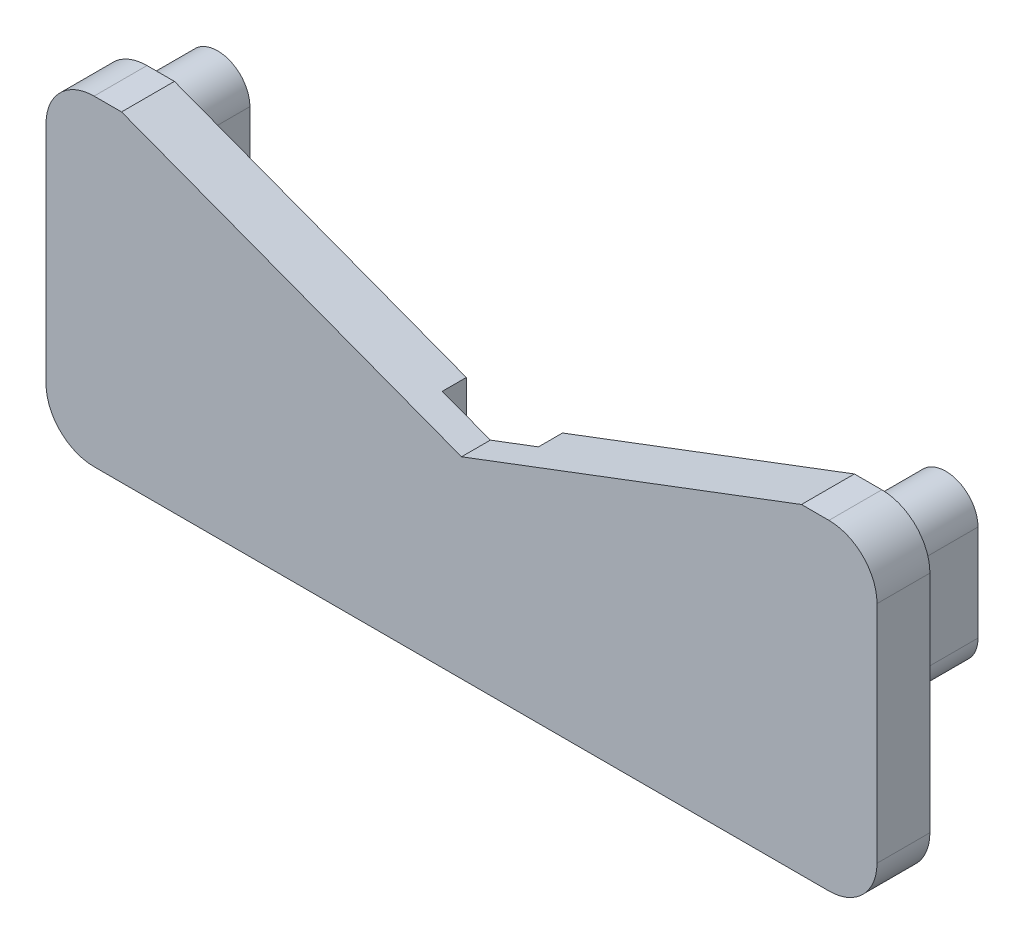
SolidWorks part; units mm, degrees
ref_plane "Front Plane" through (0, 0, 0) normal (0, 0, 1) x (1, 0, 0)
ref_plane "Top Plane" through (0, 0, 0) normal (0, 1, 0) x (1, 0, 0)
ref_plane "Right Plane" through (0, 0, 0) normal (1, 0, 0) x (0, 0, -1)
sketch "Sketch1" plane through (0, 0, 0) normal (0, 0, 1) x (1, 0, 0)
  line L0 (-37.85, 11.3382) -> (-37.85, 1.3382) construction
  line L1 (-38.2, -16.6882) -> (38.2, -16.6882)
  line L2 (-43.2, -11.6882) -> (-43.2, 11.6882)
  line L3 (-38.2, 16.6882) -> (38.2, 16.6882)
  line L4 (43.2, -11.6882) -> (43.2, 11.6882)
  line L5 (-43.2, -16.6882) -> (43.2, 16.6882) construction
  line L6 (-43.2, 16.6882) -> (43.2, -16.6882) construction
  line L7 (-34.5, 11.3382) -> (-34.5, 1.3382)
  line L8 (-41.2, 11.3382) -> (-41.2, 1.3382)
  line L9 (37.85, 11.3382) -> (37.85, 1.3382) construction
  line L10 (41.2, 11.3382) -> (41.2, 1.3382)
  line L11 (34.5, 11.3382) -> (34.5, 1.3382)
  line L12 (-37.85, 6.3382) -> (37.85, 6.3382) construction
  line L13 (-35.3467, 16.6882) -> (0, 3.3118)
  line L14 (0, 3.3118) -> (35.3467, 16.6882)
  line L15 (-5, 5.204) -> (-5, -16.6882)
  line L16 (5, 5.204) -> (5, -16.6882)
  arc A0 (-34.5, 11.3382) -> (-41.2, 11.3382) centre (-37.85, 11.3382) ccw
  arc A1 (-41.2, 1.3382) -> (-34.5, 1.3382) centre (-37.85, 1.3382) ccw
  arc A2 (41.2, 11.3382) -> (34.5, 11.3382) centre (37.85, 11.3382) ccw
  arc A3 (34.5, 1.3382) -> (41.2, 1.3382) centre (37.85, 1.3382) ccw
  arc A4 (-38.2, -16.6882) -> (-43.2, -11.6882) centre (-38.2, -11.6882) cw
  arc A5 (38.2, -16.6882) -> (43.2, -11.6882) centre (38.2, -11.6882) ccw
  arc A6 (38.2, 16.6882) -> (43.2, 11.6882) centre (38.2, 11.6882) cw
  arc A7 (-43.2, 11.6882) -> (-38.2, 16.6882) centre (-38.2, 11.6882) cw
  point P0 (0, 0)
  point P8 (-37.85, 6.3382)
  point P13 (37.85, 6.3382)
  point P22 (0, 6.3382)
  point P42 (0, 0)
  point P43 (-5.3476, 6.4167)
  point P44 (0, 3.156)
  point P45 (-35.3467, 16.6882)
  dimension "D5" = 5
  dimension "D1" = 6.7
  dimension "D2" = 69
  dimension "D3" = 2
  dimension "D4" = 5.35
  dimension "D6" = 10
  dimension "D7" = 20
  dimension "D8" = 10
extrude "Boss-Extrude1" add sketch "Sketch1" along normal blind 2.5 contours L8 A1 L7 A0 | L11 A3 L10 A2 | A7 L2 A4 L1 L15 L13 L3 A1 L8 A0 L7 | A6 L3 L14 L16 L1 A5 L4 A3 L11 A2 L10 region at (-24.0662, -2.9249, 0) region at (24.0662, -2.9249, 0) region at (-37.85, 6.3382, 0) region at (37.85, 6.3382, 0)
extrude "Boss-Extrude3" add sketch "Sketch1<4>" along normal blind 3 from surface contours A7 L2 A4 L1 L15 L13 L3 A1 L8 A0 L7 | L16 L14 L13 L15 L1 | A6 L3 L14 L16 L1 A5 L4 A3 L11 A2 L10 | L11 A3 L10 A2 | L8 A1 L7 A0 region at (-24.0662, -2.9249, 0) region at (0, -6.208, 0) region at (24.0662, -2.9249, 0) region at (-37.85, 6.3382, 0) region at (37.85, 6.3382, 0) starting at face at (-30.0311, 0.7434, 2.5)
sketch "Sketch1<4>" plane through (0, 0, 0) normal (0, 0, 1) x (1, 0, 0) same geometry as "Sketch1"
extrude "Boss-Extrude2" add sketch "Sketch1<3>" against normal blind 7 contours L11 A3 L10 A2 | L8 A1 L7 A0 region at (-37.85, 6.3382, 0) region at (37.85, 6.3382, 0)
sketch "Sketch1<3>" plane through (0, 0, 0) normal (0, 0, 1) x (1, 0, 0) same geometry as "Sketch1"
equation "\"D4@Sketch1\"=\"D1@Sketch1\"/2 + \"D3@Sketch1\""
